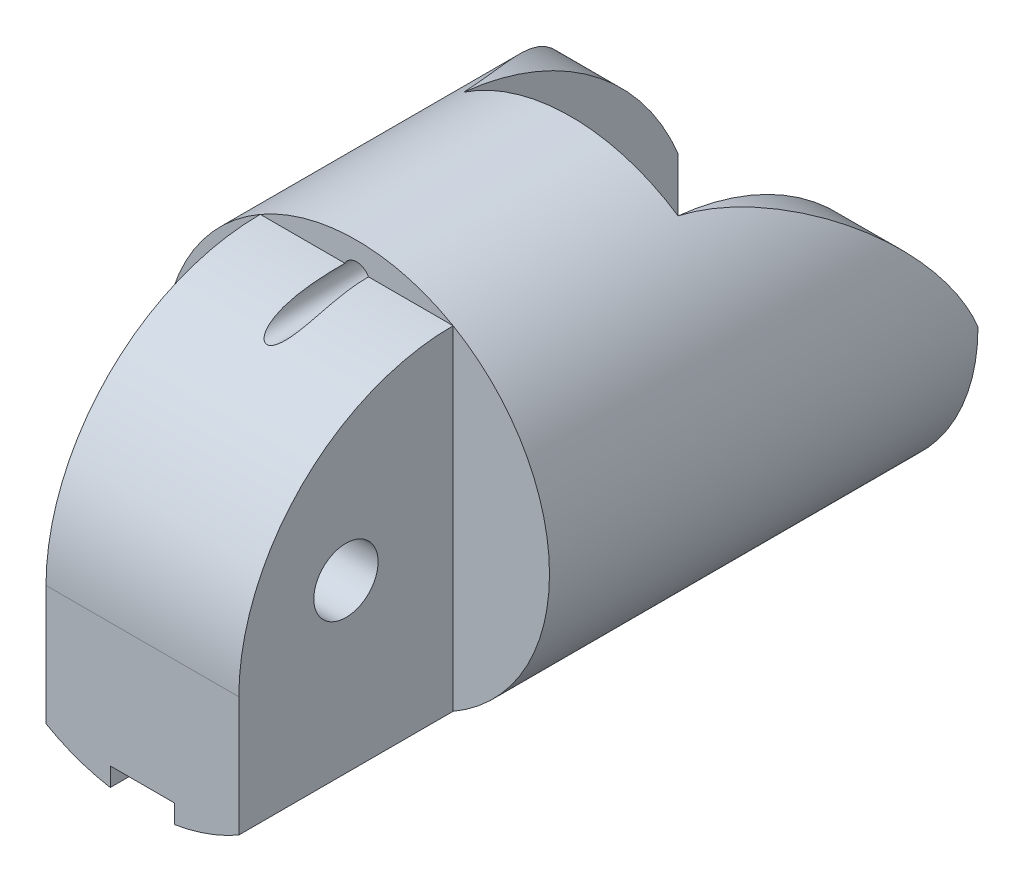
SolidWorks part; units mm, degrees
ref_plane "Front Plane" through (0, 0, 0) normal (0, 0, 1) x (1, 0, 0)
ref_plane "Top Plane" through (0, 0, 0) normal (0, 1, 0) x (1, 0, 0)
ref_plane "Right Plane" through (0, 0, 0) normal (1, 0, 0) x (0, 0, -1)
sketch "Sketch1" plane through (0, 0, 0) normal (0, 0, 1) x (1, 0, 0)
  circle A0 centre (0, 0) radius 9
extrude "Boss-Extrude1" add sketch "Sketch1" against normal blind 20
sketch "Sketch2" plane through (0, 0, 0) normal (0, 1, 0) x (1, 0, 0)
  line L0 (0, 20) -> (0, 0) construction
  line L1 (9, 20) -> (-9, 20) construction
  line L2 (-9, 10) -> (9, 10) construction
  line L3 (-9, 20) -> (-9, 0) construction
  line L4 (9, 0) -> (9, 20) construction
  line L5 (5, 20) -> (5, 10)
  line L6 (5, 20) -> (-5, 20)
  line L8 (5, 10) -> (-5, 10)
  line L9 (-5, 20) -> (-5, 10)
extrude "Cut-Extrude1" cut sketch "Sketch2" against normal through all both and the other way through all
sketch "Sketch3" plane through (0, 0, 0) normal (0, 0, 1) x (1, 0, 0)
  line L0 (0, 9) -> (0, -9) construction
  line L1 (-4.5, 7.7942) -> (-4.5, -7.7942)
  line L2 (4.5, 7.7942) -> (4.5, -7.7942)
  line L3 (-4.5, 7.7942) -> (4.5, 7.7942)
  circle A0 centre (0, 0) radius 9 construction
  arc A1 (-4.5, -7.7942) -> (4.5, -7.7942) centre (0, 0) ccw
extrude "Boss-Extrude2" add sketch "Sketch3" along normal blind 10
sketch "Sketch4" plane through (0, 0, 0) normal (1, 0, 0) x (0, 0, -1)
  line L0 (20, -7.4833) -> (20, 7.4833) construction
  circle A0 centre (-5, 0) radius 1.5
  circle A1 centre (16, 0) radius 1.5
  dimension "D1" = 4
extrude "Cut-Extrude2" cut sketch "Sketch4" along normal blind 8 and the other way through all contours A0 | A1
fillet "Fillet1" radius 10 1 edges at (0, 7.7942, 10)
sketch "Sketch5" plane through (0, 0, 0) normal (1, 0, 0) x (0, 0, -1)
  line L0 (20, -7.4833) -> (20, 7.4833) construction
  line L1 (10, 7.4833) -> (20, 7.4833)
  line L2 (20, 7.4833) -> (20, 0)
  arc A0 (10, 7.4833) -> (20, 0) centre (8.7287, -4.6387) cw
extrude "Cut-Extrude3" cut sketch "Sketch5" against normal through all both and the other way through all
sketch "Sketch6" plane through (0, 0, -20) normal (0, 0, -1) x (-1, 0, 0)
  circle A0 centre (0, 7.5) radius 0.625
  dimension "D1" = 1.25
extrude "Cut-Extrude4" cut sketch "Sketch6" against normal blind 32
sketch "Sketch7" plane through (0, 0, -10) normal (0, 0, -1) x (-1, 0, 0)
  line L1 (-1.5, -10) -> (1.5, -10)
  line L2 (-1.5, -10) -> (-1.5, -8)
  line L3 (-1.5, -8) -> (1.5, -8)
  line L4 (1.5, -10) -> (1.5, -8)
  line L5 (-1.5, -10) -> (1.5, -8) construction
  line L6 (-1.5, -8) -> (1.5, -10) construction
  arc A0 (-5, -7.4833) -> (5, -7.4833) centre (0, 0) ccw construction
  point P0 (0, -9)
extrude "Cut-Extrude5" cut sketch "Sketch7" against normal up to next
sketch "Sketch8" plane through (0, -8, 0) normal (0, -1, 0) x (-1, 0, 0)
  circle A0 centre (0, 0) radius 0.9
  dimension "D1" = 1.8
extrude "Cut-Extrude6" cut sketch "Sketch8" against normal blind 5
